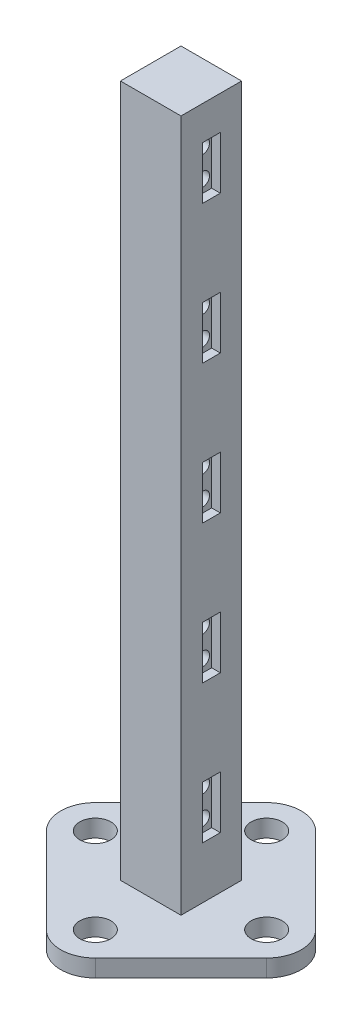
SolidWorks part; units mm, degrees
ref_plane "Front" through (0, 0, 0) normal (0, 0, 1) x (1, 0, 0)
ref_plane "Top" through (0, 0, 0) normal (0, 1, 0) x (1, 0, 0)
ref_plane "Right" through (0, 0, 0) normal (1, 0, 0) x (0, 0, -1)
ref_axis "Axis1" through (0, 55, 0) along (0, -1, 0)
ref_axis "Axis2" through (88.99, 0, 0) along (-1, 0, 0)
ref_axis "Axis3" through (0, 0, 55) along (0, 0, -1)
sketch "Sketch1" plane through (0, 0, 0) normal (0, 1, 0) x (1, 0, 0)
  line L0 (-24.75, 0) -> (0, 24.75) construction
  line L9 (-24.75, 0) -> (0, -24.75) construction
  line L11 (0, 24.75) -> (24.75, 0) construction
  line L12 (0, -24.75) -> (24.75, 0) construction
  line L13 (-24.75, 0) -> (24.75, 0) construction
  line L14 (0, 24.75) -> (0, -24.75) construction
  line L15 (-31.8211, 7.0711) -> (-7.0711, 31.8211)
  line L16 (7.0711, 31.8211) -> (31.8211, 7.0711)
  line L17 (7.0711, -31.8211) -> (31.8211, -7.0711)
  line L18 (-31.8211, -7.0711) -> (-7.0711, -31.8211)
  line L19 (0, -38.8921) -> (38.8921, 0) construction
  line L20 (-38.8921, 0) -> (0, -38.8921) construction
  line L21 (0, 38.8921) -> (38.8921, 0) construction
  line L22 (-38.8921, 0) -> (0, 38.8921) construction
  arc A4 (7.0711, -31.8211) -> (-7.0711, -31.8211) centre (0, -24.75) cw
  arc A5 (31.8211, 7.0711) -> (31.8211, -7.0711) centre (24.75, 0) cw
  arc A6 (-7.0711, 31.8211) -> (7.0711, 31.8211) centre (0, 24.75) cw
  arc A7 (-31.8211, 7.0711) -> (-31.8211, -7.0711) centre (-24.75, 0) ccw
  circle A8 centre (0, 24.75) radius 4.5
  circle A9 centre (24.75, 0) radius 4.5
  circle A10 centre (0, -24.75) radius 4.5
  circle A11 centre (-24.75, 0) radius 4.5
  point P1 (0, 0)
  dimension "D3" = 10
  dimension "D4" = 9
  dimension "D1" = 49.5
  dimension "D2" = 10
extrude "Boss-Extrude1" add sketch "Sketch1" along normal mid plane 5
sketch "Sketch2" plane through (0, 2.5, 0) normal (0, 1, 0) x (1, 0, 0)
  line L0 (-8.75, 8.75) -> (8.75, -8.75) construction
  line L1 (-8.75, 8.75) -> (8.75, 8.75)
  line L2 (-8.75, 8.75) -> (-8.75, -8.75)
  line L3 (-8.75, -8.75) -> (8.75, -8.75)
  line L4 (8.75, 8.75) -> (8.75, -8.75)
  line L5 (-7.0711, 31.8211) -> (-31.8211, 7.0711) construction
  dimension "D1" = 17.5
extrude "Boss-Extrude2" add sketch "Sketch2" along normal blind 200
sketch "Sketch3" plane through (8.75, 0, 0) normal (1, 0, 0) x (0, 0, -1)
  line L0 (7.0711, 2.5) -> (31.8211, 2.5) construction
  line L1 (-2.6, 17.5) -> (2.6, 17.5)
  line L2 (-2.6, 17.5) -> (-2.6, 32.7)
  line L3 (-2.6, 32.7) -> (2.6, 32.7)
  line L4 (2.6, 17.5) -> (2.6, 32.7)
  point P4 (0, 17.5)
  dimension "D1" = 5.2
  dimension "D2" = 15.2
  dimension "D3" = 15
extrude "Cut-Extrude1" cut sketch "Sketch3" against normal blind 2.5
hole_wizard "Ø4.0mm Dowel Hole1" positions "Sketch5" profile "Sketch6" hole size "Ø4.0" standard "DIN" end condition through all
sketch "Sketch5" plane through (6.25, 0, 0) normal (1, 0, 0) x (0, 0, -1)
  line L0 (0, 32.7) -> (0, 29.2) construction
  line L1 (2.6, 32.7) -> (-2.6, 32.7) construction
  line L2 (0, 29.2) -> (0, 21) construction
  line L3 (0, 21) -> (0, 17.5) construction
  line L4 (-2.6, 17.5) -> (2.6, 17.5) construction
  point P0 (0, 21)
  point P2 (0, 29.2)
  dimension "D1" = 3.5
sketch "Sketch6" plane through (6.25, 21, 0) normal (0, 1, 0) x (0, 0, -1)
  line L0 (0, 0) -> (0, 41)
  line L1 (0, 41) -> (2, 41)
  line L2 (2, 41) -> (2, 0)
  line L5 (2, 0) -> (0, 0)
  line L11 (0, -6.35) -> (0, 107.95) construction
  dimension "Thru Hole Dia." = 4
  dimension "Thru Hole Depth" = 41
pattern_linear "LPattern1" count 5 spacing 40 along (0, 1, 0) of "Ø4.0mm Dowel Hole1", "Cut-Extrude1"
